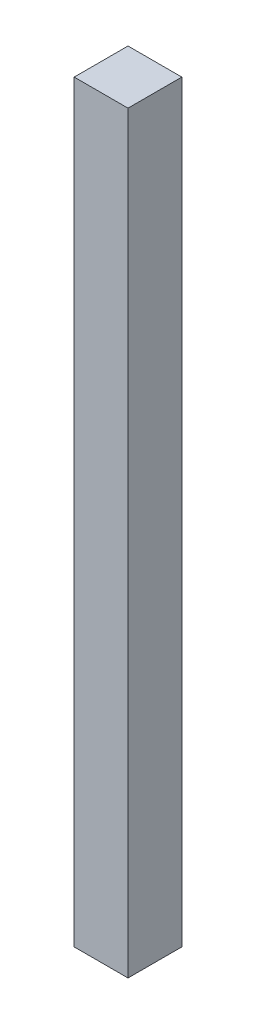
SolidWorks part; units mm, degrees
material "Mahogany"
ref_plane "Plan de face" through (0, 0, 0) normal (0, 0, 1) x (1, 0, 0)
ref_plane "Plan de dessus" through (0, 0, 0) normal (0, 1, 0) x (1, 0, 0)
ref_plane "Plan de droite" through (0, 0, 0) normal (1, 0, 0) x (0, 0, -1)
sketch "Sketch2" plane through (0, 0, 0) normal (0, 1, 0) x (1, 0, 0)
  line L1 (0, 0) -> (25, 0)
  line L2 (0, 0) -> (0, 25)
  line L3 (0, 25) -> (25, 25)
  line L4 (25, 0) -> (25, 25)
  dimension "D1" = 25
  dimension "D2" = 25
extrude "Boss-Extrude1" add sketch "Sketch2" along normal blind 350
